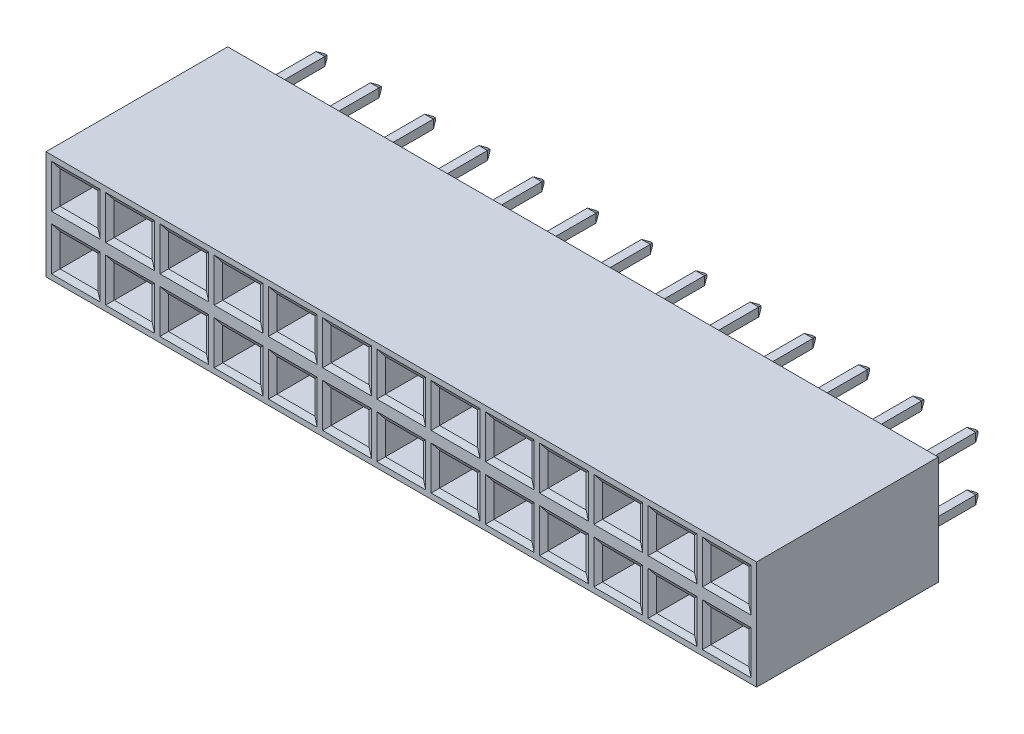
SolidWorks part; units mm, degrees
ref_plane "Front Plane" through (0, 0, 0) normal (0, 0, 1) x (1, 0, 0)
ref_plane "Top Plane" through (0, 0, 0) normal (0, 1, 0) x (1, 0, 0)
ref_plane "Right Plane" through (0, 0, 0) normal (1, 0, 0) x (0, 0, -1)
sketch "Sketch1" plane through (0, 0, 0) normal (0, 0, 1) x (1, 0, 0)
  line L1 (1.397, -1.27) -> (-1.397, -1.27)
  line L2 (1.397, -1.27) -> (1.397, 1.27)
  line L3 (1.397, 1.27) -> (-1.397, 1.27)
  line L4 (-1.397, -1.27) -> (-1.397, 1.27)
  line L5 (1.397, -1.27) -> (-1.397, 1.27) construction
  line L6 (1.397, 1.27) -> (-1.397, -1.27) construction
  point P0 (0, 0)
  dimension "D1" = 2.54
  dimension "D2" = 2.794
extrude "Boss-Extrude1" add sketch "Sketch1" along normal mid plane 8.509
sketch "Sketch4" plane through (0, 0, 4.2545) normal (0, 0, 1) x (1, 0, 0)
  line L0 (0.889, 0) -> (1.397, 0) construction
  line L1 (-0.889, -0.762) -> (0.889, -0.762)
  line L2 (-0.889, -0.762) -> (-0.889, 0.762)
  line L3 (-0.889, 0.762) -> (0.889, 0.762)
  line L4 (0.889, -0.762) -> (0.889, 0.762)
  line L5 (-0.889, -0.762) -> (0.889, 0.762) construction
  line L6 (-0.889, 0.762) -> (0.889, -0.762) construction
  line L7 (1.397, -1.27) -> (1.397, 1.27) construction
  line L8 (0, 0.762) -> (0, 1.27) construction
  line L9 (1.397, 1.27) -> (-1.397, 1.27) construction
  point P0 (0, 0)
  dimension "D1" = 0.508
extrude "Cut-Extrude1" cut sketch "Sketch4" against normal blind 6.35
chamfer "Chamfer2" distance 0.254 angle 30 4 edges at (-0.889, 0, 4.2545) (0, 0.762, 4.2545) (0.889, 0, 4.2545) (0, -0.762, 4.2545) first distance on face at (0, 0, 4.2545)
sketch "Sketch6" plane through (0, 0, -4.2545) normal (0, 0, -1) x (-1, 0, 0)
  line L1 (-0.2032, -0.2032) -> (0.2032, -0.2032)
  line L2 (-0.2032, -0.2032) -> (-0.2032, 0.2032)
  line L3 (-0.2032, 0.2032) -> (0.2032, 0.2032)
  line L4 (0.2032, -0.2032) -> (0.2032, 0.2032)
  line L5 (-0.2032, -0.2032) -> (0.2032, 0.2032) construction
  line L6 (-0.2032, 0.2032) -> (0.2032, -0.2032) construction
  point P0 (0, 0)
  dimension "D1" = 0.4064
extrude "Boss-Extrude2" add sketch "Sketch6" along normal blind 3.2004
chamfer "Chamfer3" distance 0.254 angle 30 4 edges at (0, -0.2032, -7.4549) (-0.2032, 0, -7.4549) (0, 0.2032, -7.4549) (0.2032, 0, -7.4549) first distance on face at (0, -0.2032, -5.8547) first distance on face at (-0.2032, 0, -5.8547) first distance on face at (0, 0.2032, -5.8547) first distance on face at (0.2032, 0, -5.8547)
pattern_linear "LPattern1" count 13 spacing 2.54 along (1, 0, 0) count 2 spacing 2.54 along (0, -1, 0) of "Boss-Extrude1", "Cut-Extrude1", "Chamfer2", "Boss-Extrude2", "Chamfer3"
ref_point "Point2"
ref_point "Point3"
